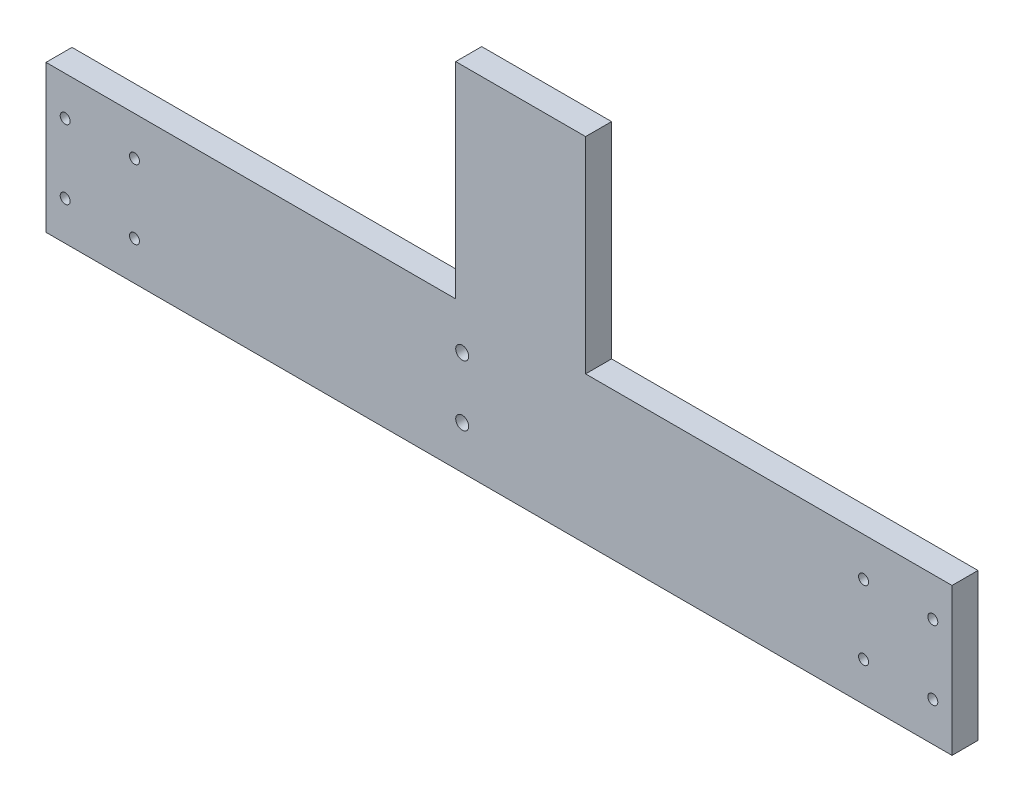
SolidWorks part; units mm, degrees
ref_plane "Plan de face" through (0, 0, 0) normal (0, 0, 1) x (1, 0, 0)
ref_plane "Plan de dessus" through (0, 0, 0) normal (0, 1, 0) x (1, 0, 0)
ref_plane "Plan de droite" through (0, 0, 0) normal (1, 0, 0) x (0, 0, -1)
sketch "Esquisse1" plane through (0, 0, 0) normal (0, 0, 1) x (1, 0, 0)
  line L0 (-104.63, 17) -> (-10, 17)
  line L1 (104.63, 17) -> (20, 17)
  line L2 (-104.63, 17) -> (-104.63, -17)
  line L3 (-104.63, -17) -> (104.63, -17)
  line L4 (104.63, 17) -> (104.63, -17)
  line L6 (-10, 17) -> (-10, 64.471)
  line L7 (-10, 64.471) -> (20, 64.471)
  line L8 (20, 17) -> (20, 64.471)
  dimension "D1" = 209.26
  dimension "D2" = 34
  dimension "D3" = 104.63
  dimension "D5" = 47.471
  dimension "D6" = 30
  dimension "D7" = 94.63
extrude "Boss.-Extru.1" add sketch "Esquisse1" along normal blind 6
sketch "Esquisse2" plane through (0, 0, 6) normal (0, 0, 1) x (1, 0, 0)
  line L0 (0, 49.0616) -> (0, -42.9956) construction
  line L1 (-104.63, 17) -> (-104.63, -17) construction
  line L3 (-104.63, -17) -> (104.63, -17) construction
  line L4 (-10, 17) -> (-104.63, 17) construction
  line L5 (-104.63, 17) -> (-104.63, -17) construction
  circle A0 centre (-100.2, 8) radius 1.15
  circle A1 centre (-84.2, 8) radius 1.15
  circle A2 centre (-84.2, -8) radius 1.15
  circle A3 centre (-100.2, -8) radius 1.15
  circle A4 centre (100.2, -8) radius 1.15
  circle A5 centre (84.2, -8) radius 1.15
  circle A6 centre (84.2, 8) radius 1.15
  circle A7 centre (100.2, 8) radius 1.15
  circle A8 centre (-8.5, 7) radius 1.5
  circle A9 centre (-8.5, -7) radius 1.5
  dimension "D1" = 2.3
  dimension "D2" = 2.3
  dimension "D3" = 2.3
  dimension "D4" = 2.3
  dimension "D12" = 3
  dimension "D14" = 3
  dimension "D5" = 4.43
  dimension "D6" = 9
  dimension "D7" = 9
  dimension "D8" = 16
  dimension "D9" = 16
  dimension "D10" = 16
  dimension "D11" = 16
  dimension "D13" = 10
  dimension "D15" = 10
  dimension "D16" = 14
  dimension "D17" = 8.5
  dimension "D18" = 4.43
extrude "Enlèv. mat.-Extru.1" cut sketch "Esquisse2" against normal blind 6
